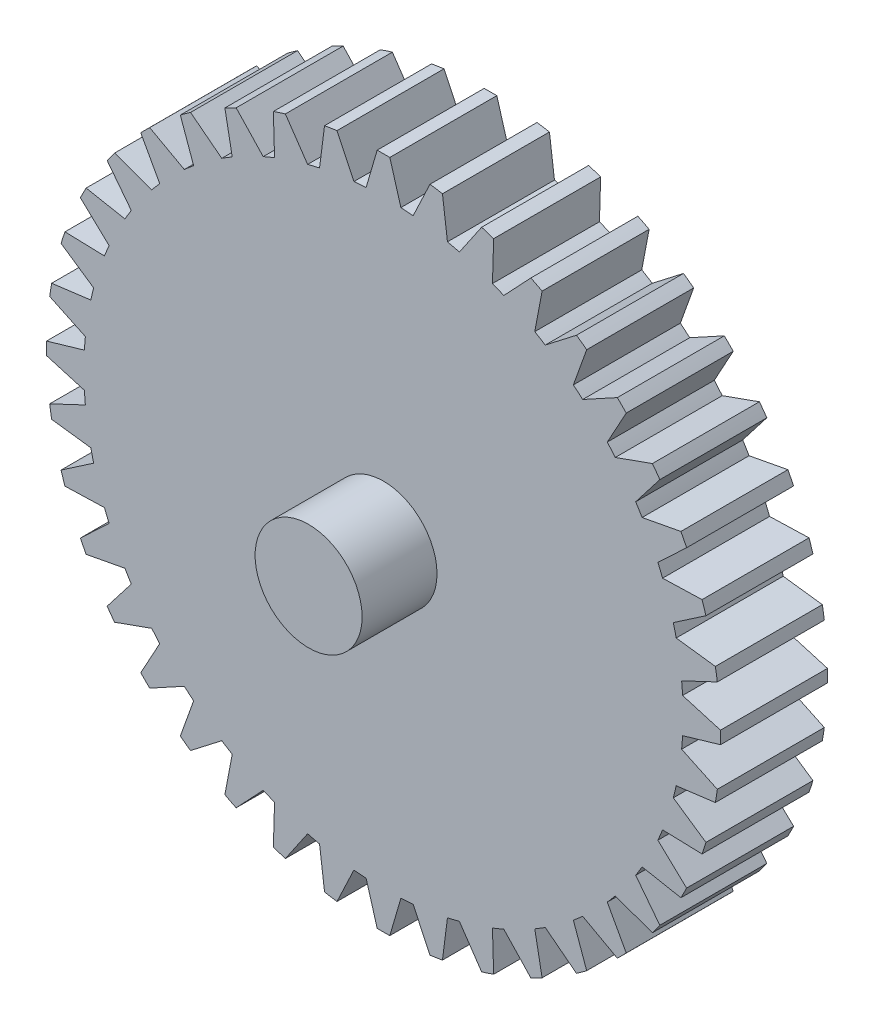
SolidWorks part; units mm, degrees
ref_plane "Front Plane" through (0, 0, 0) normal (0, 0, 1) x (1, 0, 0)
ref_plane "Top Plane" through (0, 0, 0) normal (0, 1, 0) x (1, 0, 0)
ref_plane "Right Plane" through (0, 0, 0) normal (1, 0, 0) x (0, 0, -1)
sketch "Sketch1" plane through (0, 0, 0) normal (0, 0, 1) x (1, 0, 0)
  line L0 (93.5, 343.5) -> (593.5, 343.5) construction
  line L1 (4.3441, 31.199) -> (2.7678, 27.8629)
  line L2 (5.5096, 31.0144) -> (5.9778, 27.3545)
  line L3 (9.1712, 30.1353) -> (7.0924, 27.0869)
  line L4 (10.2935, 29.7707) -> (10.1834, 26.0825)
  line L5 (13.7725, 28.3296) -> (11.2424, 25.6439)
  line L6 (-0.59, 31.4945) -> (-1.625, 27.9528)
  line L7 (0.59, 31.4945) -> (1.625, 27.9528)
  line L8 (-0.59, 31.4945) -> (0.59, 31.4945)
  line L9 (14.8239, 27.7939) -> (14.1382, 24.1684)
  line L10 (18.0347, 25.8264) -> (15.1156, 23.5694)
  line L11 (18.9893, 25.1328) -> (17.7449, 21.6591)
  line L12 (21.8528, 22.6871) -> (18.6166, 20.9147)
  line L13 (22.6871, 21.8528) -> (20.9147, 18.6166)
  line L14 (25.1328, 18.9893) -> (21.6591, 17.7449)
  line L15 (25.8264, 18.0347) -> (23.5694, 15.1156)
  line L16 (27.7939, 14.8239) -> (24.1684, 14.1382)
  line L17 (28.3296, 13.7725) -> (25.6439, 11.2424)
  line L18 (29.7707, 10.2935) -> (26.0825, 10.1834)
  line L19 (30.1353, 9.1712) -> (27.0869, 7.0924)
  line L20 (31.0144, 5.5096) -> (27.3545, 5.9778)
  line L21 (31.199, 4.3441) -> (27.8629, 2.7678)
  line L22 (31.4945, 0.59) -> (27.9528, 1.625)
  line L23 (31.4945, -0.59) -> (27.9528, -1.625)
  line L24 (31.199, -4.3441) -> (27.8629, -2.7678)
  line L25 (31.0144, -5.5096) -> (27.3545, -5.9778)
  line L26 (30.1353, -9.1712) -> (27.0869, -7.0924)
  line L27 (29.7707, -10.2935) -> (26.0825, -10.1834)
  line L28 (28.3296, -13.7725) -> (25.6439, -11.2424)
  line L29 (27.7939, -14.8239) -> (24.1684, -14.1382)
  line L30 (25.8264, -18.0347) -> (23.5694, -15.1156)
  line L31 (25.1328, -18.9893) -> (21.6591, -17.7449)
  line L32 (22.6871, -21.8528) -> (20.9147, -18.6166)
  line L33 (21.8528, -22.6871) -> (18.6166, -20.9147)
  line L34 (18.9893, -25.1328) -> (17.7449, -21.6591)
  line L35 (18.0347, -25.8264) -> (15.1156, -23.5694)
  line L36 (14.8239, -27.7939) -> (14.1382, -24.1684)
  line L37 (13.7725, -28.3296) -> (11.2424, -25.6439)
  line L38 (10.2935, -29.7707) -> (10.1834, -26.0825)
  line L39 (9.1712, -30.1353) -> (7.0924, -27.0869)
  line L40 (5.5096, -31.0144) -> (5.9778, -27.3545)
  line L41 (4.3441, -31.199) -> (2.7678, -27.8629)
  line L42 (0.59, -31.4945) -> (1.625, -27.9528)
  line L43 (-0.59, -31.4945) -> (-1.625, -27.9528)
  line L44 (-4.3441, -31.199) -> (-2.7678, -27.8629)
  line L45 (-5.5096, -31.0144) -> (-5.9778, -27.3545)
  line L46 (-9.1712, -30.1353) -> (-7.0924, -27.0869)
  line L47 (-10.2935, -29.7707) -> (-10.1834, -26.0825)
  line L48 (-13.7725, -28.3296) -> (-11.2424, -25.6439)
  line L49 (-14.8239, -27.7939) -> (-14.1382, -24.1684)
  line L50 (-18.0347, -25.8264) -> (-15.1156, -23.5694)
  line L51 (-18.9893, -25.1328) -> (-17.7449, -21.6591)
  line L52 (-21.8528, -22.6871) -> (-18.6166, -20.9147)
  line L53 (-22.6871, -21.8528) -> (-20.9147, -18.6166)
  line L54 (-25.1328, -18.9893) -> (-21.6591, -17.7449)
  line L55 (-25.8264, -18.0347) -> (-23.5694, -15.1156)
  line L56 (-27.7939, -14.8239) -> (-24.1684, -14.1382)
  line L57 (-28.3296, -13.7725) -> (-25.6439, -11.2424)
  line L58 (-29.7707, -10.2935) -> (-26.0825, -10.1834)
  line L59 (-30.1353, -9.1712) -> (-27.0869, -7.0924)
  line L60 (-31.0144, -5.5096) -> (-27.3545, -5.9778)
  line L61 (-31.199, -4.3441) -> (-27.8629, -2.7678)
  line L62 (-31.4945, -0.59) -> (-27.9528, -1.625)
  line L63 (-31.4945, 0.59) -> (-27.9528, 1.625)
  line L64 (-31.199, 4.3441) -> (-27.8629, 2.7678)
  line L65 (-31.0144, 5.5096) -> (-27.3545, 5.9778)
  line L66 (-30.1353, 9.1712) -> (-27.0869, 7.0924)
  line L67 (-29.7707, 10.2935) -> (-26.0825, 10.1834)
  line L68 (-28.3296, 13.7725) -> (-25.6439, 11.2424)
  line L69 (-27.7939, 14.8239) -> (-24.1684, 14.1382)
  line L70 (-25.8264, 18.0347) -> (-23.5694, 15.1156)
  line L71 (-25.1328, 18.9893) -> (-21.6591, 17.7449)
  line L72 (-22.6871, 21.8528) -> (-20.9147, 18.6166)
  line L73 (-21.8528, 22.6871) -> (-18.6166, 20.9147)
  line L74 (-18.9893, 25.1328) -> (-17.7449, 21.6591)
  line L75 (-18.0347, 25.8264) -> (-15.1156, 23.5694)
  line L76 (-14.8239, 27.7939) -> (-14.1382, 24.1684)
  line L77 (-13.7725, 28.3296) -> (-11.2424, 25.6439)
  line L78 (-10.2935, 29.7707) -> (-10.1834, 26.0825)
  line L79 (-9.1712, 30.1353) -> (-7.0924, 27.0869)
  line L80 (-5.5096, 31.0144) -> (-5.9778, 27.3545)
  line L81 (-4.3441, 31.199) -> (-2.7678, 27.8629)
  line L83 (16.5, -3.65) -> (-16.5, -3.65)
  line L84 (16.5, -3.65) -> (16.5, 3.65)
  line L85 (16.5, 3.65) -> (-16.5, 3.65)
  line L86 (-16.5, -3.65) -> (-16.5, 3.65)
  line L87 (16.5, -3.65) -> (-16.5, 3.65) construction
  line L88 (16.5, 3.65) -> (-16.5, -3.65) construction
  arc A2 (0.59, 31.4945) -> (-0.59, 31.4945) centre (0, 0) ccw
  arc A3 (7.0924, 27.0869) -> (5.9778, 27.3545) centre (0, 0) ccw
  arc A4 (5.5096, 31.0144) -> (4.3441, 31.199) centre (0, 0) ccw
  arc A5 (10.2935, 29.7707) -> (9.1712, 30.1353) centre (0, 0) ccw
  arc A6 (2.7678, 27.8629) -> (1.625, 27.9528) centre (0, 0) ccw
  arc A7 (-1.625, 27.9528) -> (-2.7678, 27.8629) centre (0, 0) ccw
  arc A8 (14.8239, 27.7939) -> (13.7725, 28.3296) centre (0, 0) ccw
  arc A9 (11.2424, 25.6439) -> (10.1834, 26.0825) centre (0, 0) ccw
  arc A10 (18.9893, 25.1328) -> (18.0347, 25.8264) centre (0, 0) ccw
  arc A11 (22.6871, 21.8528) -> (21.8528, 22.6871) centre (0, 0) ccw
  arc A12 (25.8264, 18.0347) -> (25.1328, 18.9893) centre (0, 0) ccw
  arc A13 (28.3296, 13.7725) -> (27.7939, 14.8239) centre (0, 0) ccw
  arc A14 (30.1353, 9.1712) -> (29.7707, 10.2935) centre (0, 0) ccw
  arc A15 (31.199, 4.3441) -> (31.0144, 5.5096) centre (0, 0) ccw
  arc A16 (31.4945, -0.59) -> (31.4945, 0.59) centre (0, 0) ccw
  arc A17 (31.0144, -5.5096) -> (31.199, -4.3441) centre (0, 0) ccw
  arc A18 (29.7707, -10.2935) -> (30.1353, -9.1712) centre (0, 0) ccw
  arc A19 (27.7939, -14.8239) -> (28.3296, -13.7725) centre (0, 0) ccw
  arc A20 (25.1328, -18.9893) -> (25.8264, -18.0347) centre (0, 0) ccw
  arc A21 (21.8528, -22.6871) -> (22.6871, -21.8528) centre (0, 0) ccw
  arc A22 (18.0347, -25.8264) -> (18.9893, -25.1328) centre (0, 0) ccw
  arc A23 (13.7725, -28.3296) -> (14.8239, -27.7939) centre (0, 0) ccw
  arc A24 (9.1712, -30.1353) -> (10.2935, -29.7707) centre (0, 0) ccw
  arc A25 (4.3441, -31.199) -> (5.5096, -31.0144) centre (0, 0) ccw
  arc A26 (-0.59, -31.4945) -> (0.59, -31.4945) centre (0, 0) ccw
  arc A27 (-5.5096, -31.0144) -> (-4.3441, -31.199) centre (0, 0) ccw
  arc A28 (-10.2935, -29.7707) -> (-9.1712, -30.1353) centre (0, 0) ccw
  arc A29 (-14.8239, -27.7939) -> (-13.7725, -28.3296) centre (0, 0) ccw
  arc A30 (-18.9893, -25.1328) -> (-18.0347, -25.8264) centre (0, 0) ccw
  arc A31 (-22.6871, -21.8528) -> (-21.8528, -22.6871) centre (0, 0) ccw
  arc A32 (-25.8264, -18.0347) -> (-25.1328, -18.9893) centre (0, 0) ccw
  arc A33 (-28.3296, -13.7725) -> (-27.7939, -14.8239) centre (0, 0) ccw
  arc A34 (-30.1353, -9.1712) -> (-29.7707, -10.2935) centre (0, 0) ccw
  arc A35 (-31.199, -4.3441) -> (-31.0144, -5.5096) centre (0, 0) ccw
  arc A36 (-31.4945, 0.59) -> (-31.4945, -0.59) centre (0, 0) ccw
  arc A37 (-31.0144, 5.5096) -> (-31.199, 4.3441) centre (0, 0) ccw
  arc A38 (-29.7707, 10.2935) -> (-30.1353, 9.1712) centre (0, 0) ccw
  arc A39 (-27.7939, 14.8239) -> (-28.3296, 13.7725) centre (0, 0) ccw
  arc A40 (-25.1328, 18.9893) -> (-25.8264, 18.0347) centre (0, 0) ccw
  arc A41 (-21.8528, 22.6871) -> (-22.6871, 21.8528) centre (0, 0) ccw
  arc A42 (-13.7725, 28.3296) -> (-14.8239, 27.7939) centre (0, 0) ccw
  arc A43 (-18.0347, 25.8264) -> (-18.9893, 25.1328) centre (0, 0) ccw
  arc A44 (-9.1712, 30.1353) -> (-10.2935, 29.7707) centre (0, 0) ccw
  arc A45 (-4.3441, 31.199) -> (-5.5096, 31.0144) centre (0, 0) ccw
  arc A46 (15.1156, 23.5694) -> (14.1382, 24.1684) centre (0, 0) ccw
  arc A47 (18.6166, 20.9147) -> (17.7449, 21.6591) centre (0, 0) ccw
  arc A48 (24.1684, 14.1382) -> (23.5694, 15.1156) centre (0, 0) ccw
  arc A49 (21.6591, 17.7449) -> (20.9147, 18.6166) centre (0, 0) ccw
  arc A50 (26.0825, 10.1834) -> (25.6439, 11.2424) centre (0, 0) ccw
  arc A51 (27.3545, 5.9778) -> (27.0869, 7.0924) centre (0, 0) ccw
  arc A52 (27.9528, 1.625) -> (27.8629, 2.7678) centre (0, 0) ccw
  arc A53 (27.8629, -2.7678) -> (27.9528, -1.625) centre (0, 0) ccw
  arc A54 (27.0869, -7.0924) -> (27.3545, -5.9778) centre (0, 0) ccw
  arc A55 (25.6439, -11.2424) -> (26.0825, -10.1834) centre (0, 0) ccw
  arc A56 (23.5694, -15.1156) -> (24.1684, -14.1382) centre (0, 0) ccw
  arc A57 (20.9147, -18.6166) -> (21.6591, -17.7449) centre (0, 0) ccw
  arc A58 (17.7449, -21.6591) -> (18.6166, -20.9147) centre (0, 0) ccw
  arc A59 (14.1382, -24.1684) -> (15.1156, -23.5694) centre (0, 0) ccw
  arc A60 (10.1834, -26.0825) -> (11.2424, -25.6439) centre (0, 0) ccw
  arc A61 (5.9778, -27.3545) -> (7.0924, -27.0869) centre (0, 0) ccw
  arc A62 (1.625, -27.9528) -> (2.7678, -27.8629) centre (0, 0) ccw
  arc A63 (-2.7678, -27.8629) -> (-1.625, -27.9528) centre (0, 0) ccw
  arc A64 (-7.0924, -27.0869) -> (-5.9778, -27.3545) centre (0, 0) ccw
  arc A65 (-11.2424, -25.6439) -> (-10.1834, -26.0825) centre (0, 0) ccw
  arc A66 (-15.1156, -23.5694) -> (-14.1382, -24.1684) centre (0, 0) ccw
  arc A67 (-18.6166, -20.9147) -> (-17.7449, -21.6591) centre (0, 0) ccw
  arc A68 (-21.6591, -17.7449) -> (-20.9147, -18.6166) centre (0, 0) ccw
  arc A69 (-24.1684, -14.1382) -> (-23.5694, -15.1156) centre (0, 0) ccw
  arc A70 (-26.0825, -10.1834) -> (-25.6439, -11.2424) centre (0, 0) ccw
  arc A71 (-27.3545, -5.9778) -> (-27.0869, -7.0924) centre (0, 0) ccw
  arc A72 (-27.9528, -1.625) -> (-27.8629, -2.7678) centre (0, 0) ccw
  arc A73 (-27.8629, 2.7678) -> (-27.9528, 1.625) centre (0, 0) ccw
  arc A74 (-27.0869, 7.0924) -> (-27.3545, 5.9778) centre (0, 0) ccw
  arc A75 (-25.6439, 11.2424) -> (-26.0825, 10.1834) centre (0, 0) ccw
  arc A76 (-23.5694, 15.1156) -> (-24.1684, 14.1382) centre (0, 0) ccw
  arc A77 (-20.9147, 18.6166) -> (-21.6591, 17.7449) centre (0, 0) ccw
  arc A78 (-17.7449, 21.6591) -> (-18.6166, 20.9147) centre (0, 0) ccw
  arc A79 (-14.1382, 24.1684) -> (-15.1156, 23.5694) centre (0, 0) ccw
  arc A80 (-10.1834, 26.0825) -> (-11.2424, 25.6439) centre (0, 0) ccw
  arc A81 (-5.9778, 27.3545) -> (-7.0924, 27.0869) centre (0, 0) ccw
  circle A82 centre (0, 0) radius 5
  point P18 (0, 31.4945)
  point P169 (0, 0)
  dimension "D1" = 63
  dimension "D2" = 3.5
  dimension "D6" = 10
  dimension "D3" = 3.25
  dimension "D4" = 1.18
  dimension "D7" = 33
  dimension "D8" = 7.3
  dimension "D5" = 40
extrude "Boss-Extrude2" add sketch "Sketch1" along normal mid plane 10 contours L80 A81 L79 A44 L78 A80 L77 A42 L76 A79 L75 A43 L74 A78 L73 A41 L72 A77 L71 A40 L70 A76 L69 A39 L68 A75 L67 A38 L66 A74 L65 A37 L64 A73 L63 A36 L62 A72 L61 A35 L60 A71 L59 A34 L58 A70 L57 A33 L56 A69 L55 | A82 L85 L86 L83 | A82 L83 L84 L85 | L85 A82 L83 | L85 A82 | L83 A82 region at (4.7883, 30.2322, 0) region at (10.4968, 0, 0) region at (0, -4.1968, 0) region at (0, 0, 0) region at (-10.4968, 0, 0) region at (0, 4.1968, 0)
extrude "Boss-Extrude3" add sketch "Sketch1<6>" along normal blind 7 from surface contours L85 A82 L83 | L85 A82 | L83 A82 region at (0, -4.1968, 0) region at (0, 0, 0) region at (0, 4.1968, 0) starting at face at (0, 0, 5)
sketch "Sketch1<6>" plane through (0, 0, 0) normal (0, 0, 1) x (1, 0, 0) same geometry as "Sketch1"
extrude "Cut-Extrude3" cut sketch "Sketch1<8>" along normal blind 3 from surface contours A82 L83 L84 L85 | A82 L85 L86 L83 | L85 A82 L83 region at (10.4968, 0, 0) region at (0, 0, 0) region at (-10.4968, 0, 0) starting at face at (0, 0, -5)
sketch "Sketch1<8>" plane through (0, 0, 0) normal (0, 0, 1) x (1, 0, 0) same geometry as "Sketch1"
